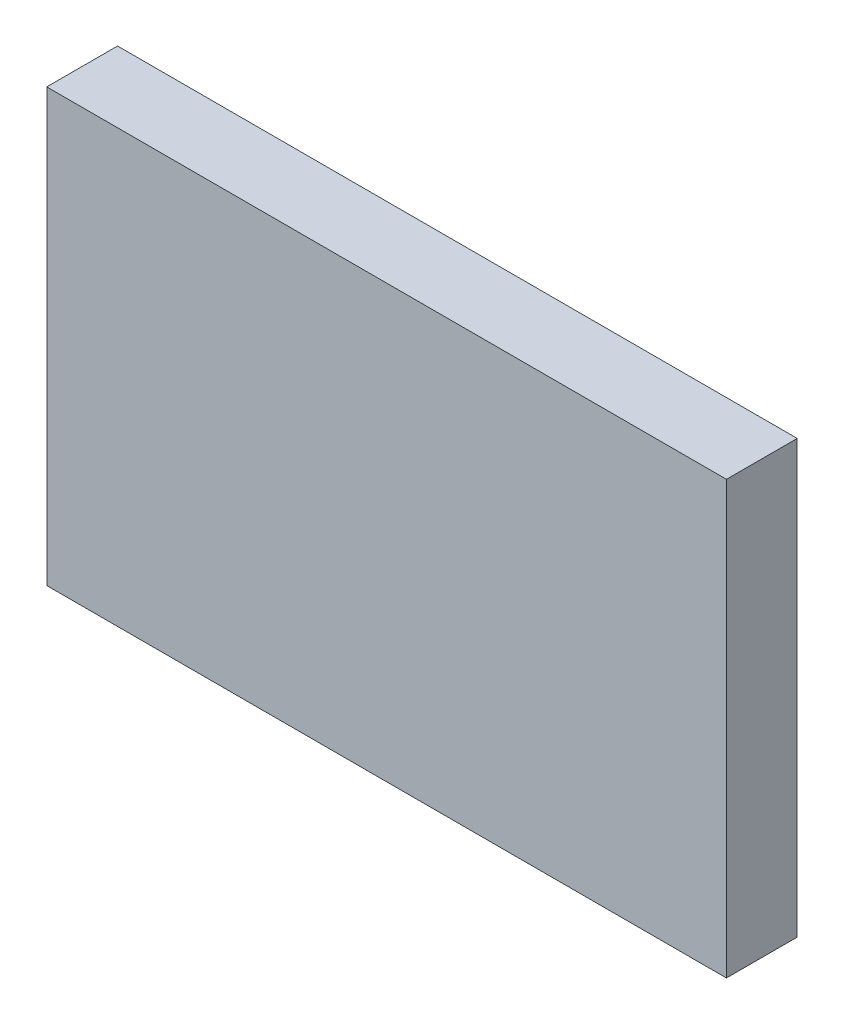
SolidWorks part; units mm, degrees
ref_plane "Ön Düzlem" through (0, 0, 0) normal (0, 0, 1) x (1, 0, 0)
ref_plane "Üst Düzlem" through (0, 0, 0) normal (0, 1, 0) x (1, 0, 0)
ref_plane "Sağ Düzlem" through (0, 0, 0) normal (1, 0, 0) x (0, 0, -1)
sketch "Çizim1" plane through (0, 0, 0) normal (0, 0, 1) x (1, 0, 0)
  line L1 (0, 0) -> (595, 0)
  line L2 (0, 0) -> (0, -194)
  line L3 (0, -194) -> (595, -194)
  line L4 (595, 0) -> (595, -194)
  dimension "D1" = 595
  dimension "D2" = 194
base flange "Taban-Flanş1" sketch "Çizim1" thickness 30 reverse thickness direction no parameters "D1"=8
sketch "Çizim2" plane through (0, 0, 0) normal (0, 0, 1) x (1, 0, 0)
  line L0 (0, -194) -> (595, -194) construction
  line L1 (595, 0) -> (288, 0)
  line L2 (595, 0) -> (595, -194)
  line L3 (595, -194) -> (288, -194)
  line L4 (288, 0) -> (288, -194)
  line L5 (0, 0) -> (0, -194) construction
  dimension "D1" = 307
  dimension "D2" = 288
extrude "Kes-Ekstrüzyon1" cut sketch "Çizim2" against normal through all both and the other way through all
sketch "Çizim3" plane through (0, 0, 0) normal (0, 0, 1) x (1, 0, 0)
  line L0 (288, 0) -> (288, -194) construction
  line L1 (0, 0) -> (288, 0)
  line L2 (0, 0) -> (0, -11)
  line L3 (0, -11) -> (288, -11)
  line L4 (288, 0) -> (288, -11)
  line L5 (0, -194) -> (288, -194) construction
  dimension "D1" = 183
extrude "Kes-Ekstrüzyon2" cut sketch "Çizim3" against normal through all both and the other way through all
sketch "Büküm-Çizgileri1" [suppressed] plane through (0, 0, 0) normal (0, 1, 0) x (1, 0, 0)
sketch "Sınırlandırma-Kutusu1" [suppressed] plane through (0, 0, 0) normal (0, 1, 0) x (1, 0, 0)
sheet metal parameters "Sac-Levha1" thickness 30 parameters "D1"=8
flat pattern "Düz-Çoğaltma1" [suppressed]
sketch "Büküm-Çizgileri2" plane through (0, 0, 0) normal (0, 1, 0) x (1, 0, 0)
sketch3d "Sınırlandırma-Kutusu2" [suppressed]
  line L0 (0, -194, 0) -> (595, -194, 0) construction
  line L1 (0, 0, 0) -> (595, 0, 0) construction
  line L2 (0, -194, 0) -> (0, 0, 0) construction
  line L3 (595, -194, 0) -> (595, 0, 0) construction
sheet metal parameters "Sac-Levha2" thickness 30 parameters "D1"=8
flat pattern "Düz-Çoğaltma1"
sketch "Büküm-Çizgileri2" plane through (0, 0, 0) normal (0, 1, 0) x (1, 0, 0)
sketch3d "Sınırlandırma-Kutusu2" [suppressed]
  line L0 (0, -194, 0) -> (288, -194, 0) construction
  line L1 (0, 0, 0) -> (288, 0, 0) construction
  line L2 (0, -194, 0) -> (0, 0, 0) construction
  line L3 (288, -194, 0) -> (288, 0, 0) construction
sheet metal parameters "Sac-Levha3" thickness 30 parameters "D1"=8
flat pattern "Düz-Çoğaltma1"
sketch "Büküm-Çizgileri2" plane through (0, 0, 0) normal (0, 1, 0) x (1, 0, 0)
sketch3d "Sınırlandırma-Kutusu2" [suppressed]
  line L0 (0, -194, 0) -> (288, -194, 0) construction
  line L1 (0, -11, 0) -> (288, -11, 0) construction
  line L2 (0, -194, 0) -> (0, -11, 0) construction
  line L3 (288, -194, 0) -> (288, -11, 0) construction
